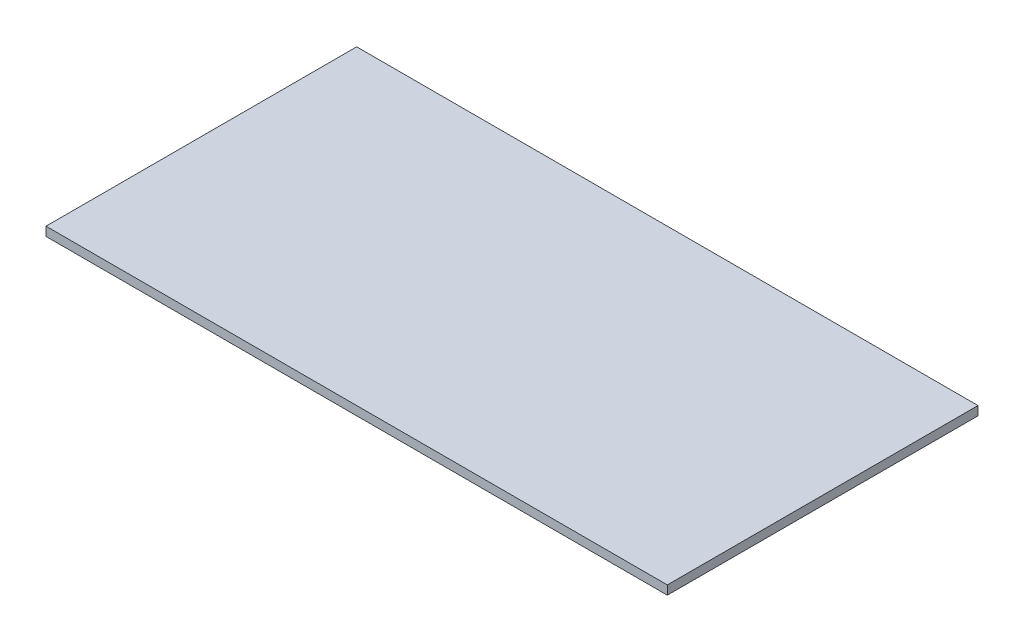
SolidWorks part; units mm, degrees
material "Cedar"
ref_plane "Front Plane" through (0, 0, 0) normal (0, 0, 1) x (1, 0, 0)
ref_plane "Top Plane" through (0, 0, 0) normal (0, 1, 0) x (1, 0, 0)
ref_plane "Right Plane" through (0, 0, 0) normal (1, 0, 0) x (0, 0, -1)
sketch "Sketch1" plane through (0, 0, 0) normal (0, 1, 0) x (1, 0, 0)
  line L1 (-609.6, -304.8) -> (609.6, -304.8)
  line L2 (-609.6, -304.8) -> (-609.6, 304.8)
  line L3 (-609.6, 304.8) -> (609.6, 304.8)
  line L4 (609.6, -304.8) -> (609.6, 304.8)
  line L5 (-609.6, -304.8) -> (609.6, 304.8) construction
  line L6 (-609.6, 304.8) -> (609.6, -304.8) construction
  point P0 (0, 0)
  dimension "D1" = 1219.2
  dimension "D2" = 609.6
extrude "Boss-Extrude1" add sketch "Sketch1" along normal blind 17.4752
